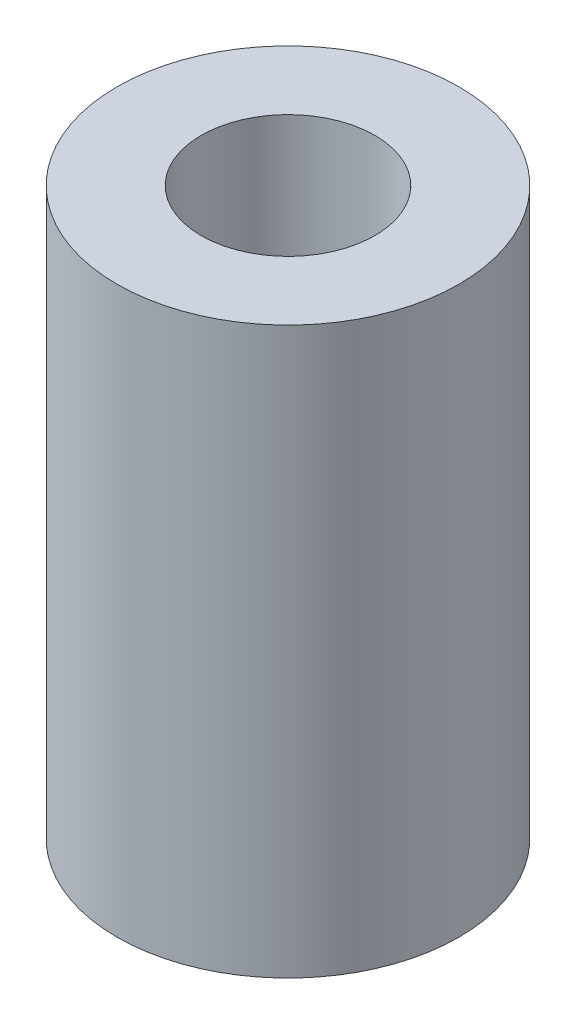
SolidWorks part; units mm, degrees
ref_plane "Front Plane" through (0, 0, 0) normal (0, 0, 1) x (1, 0, 0)
ref_plane "Top Plane" through (0, 0, 0) normal (0, 1, 0) x (1, 0, 0)
ref_plane "Right Plane" through (0, 0, 0) normal (1, 0, 0) x (0, 0, -1)
sketch "Sketch1" plane through (0, 0, 0) normal (0, 1, 0) x (1, 0, 0)
  circle A0 centre (0, 0) radius 6.35
  arc A4 (2.2922, 5.9218) -> (-4.4275, -4.5518) centre (0, 0) ccw construction
  circle A5 centre (0, 0) radius 3.2258
  circle A6 centre (0, 0) radius 3.2258
  dimension "D1" = 0.0508
extrude "Boss-Extrude1" add sketch "Sketch1" along normal up to surface (21.0005 mm away)
